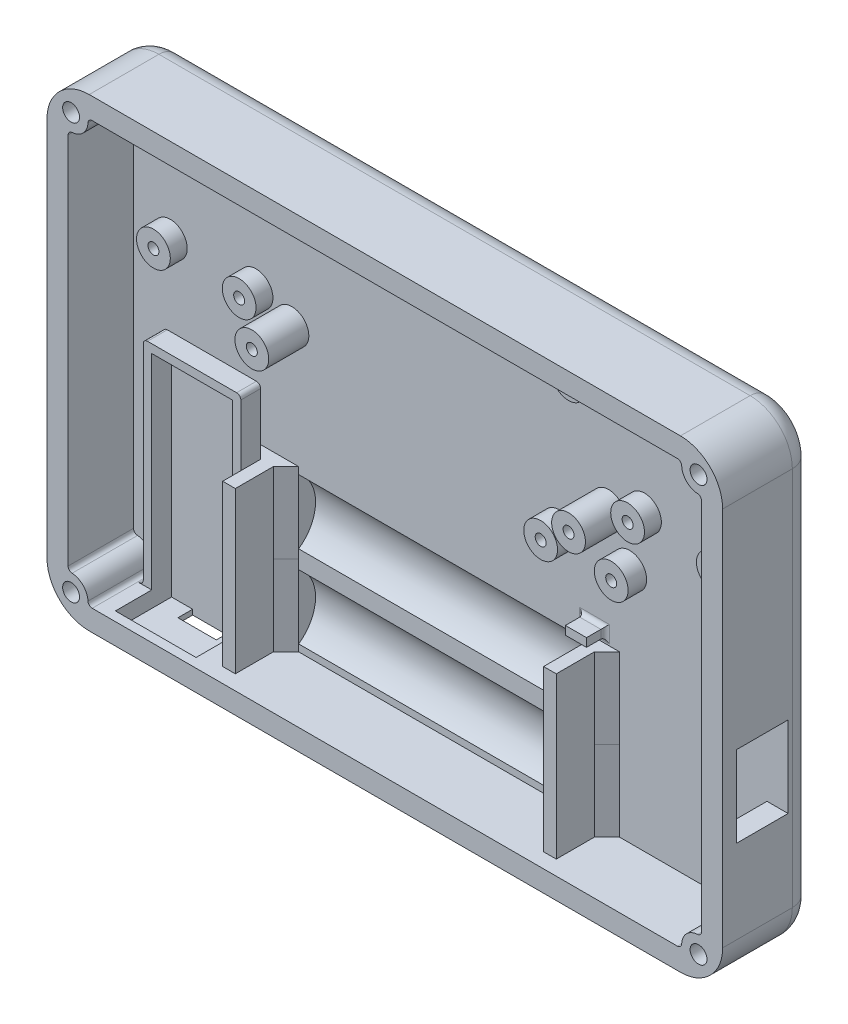
SolidWorks part; units mm, degrees
ref_plane "Ön Düzlem" through (0, 0, 0) normal (0, 0, 1) x (1, 0, 0)
ref_plane "Üst Düzlem" through (0, 0, 0) normal (0, 1, 0) x (1, 0, 0)
ref_plane "Sağ Düzlem" through (0, 0, 0) normal (1, 0, 0) x (0, 0, -1)
sketch "Çizim1" plane through (0, 0, 0) normal (0, 0, 1) x (1, 0, 0)
  line L1 (-75, -50) -> (75, -50)
  line L2 (-75, -50) -> (-75, 50)
  line L3 (-75, 50) -> (75, 50)
  line L4 (75, -50) -> (75, 50)
  line L5 (-75, -50) -> (75, 50) construction
  line L6 (-75, 50) -> (75, -50) construction
  line L7 (-80, -55) -> (80, -55)
  line L8 (-80, -55) -> (-80, 55)
  line L9 (-80, 55) -> (80, 55)
  line L10 (80, -55) -> (80, 55)
  line L11 (-80, -55) -> (80, 55) construction
  line L12 (-80, 55) -> (80, -55) construction
  point P0 (0, 0)
  point P6 (0, 0)
  dimension "D1" = 150
  dimension "D2" = 100
  dimension "D3" = 5
  dimension "D4" = 5
extrude "Yükseklik-Ekstrüzyon1" add sketch "Çizim1" along normal blind 15.5
sketch "Çizim2" plane through (0, 0, 0) normal (0, 0, -1) x (-1, 0, 0)
  line L0 (80, -55) -> (-80, -55) construction
  line L1 (80, 55) -> (80, -55) construction
  line L2 (-80, 55) -> (80, 55) construction
  line L3 (-80, -55) -> (-80, 55) construction
  line L4 (80, -55) -> (-80, -55)
  line L5 (80, 55) -> (80, -55)
  line L6 (-80, 55) -> (80, 55)
  line L7 (-80, -55) -> (-80, 55)
extrude "Yükseklik-Ekstrüzyon2" add sketch "Çizim2" along normal blind 6
fillet "Radyus1" radius 10 4 edges at (-80, -55, 4.75) (80, -55, 4.75) (80, 55, 4.75) (-80, 55, 4.75)
fillet "Radyus2" radius 5 8 edges at (77.0711, -52.0711, -6) (80, 0, -6) (77.0711, 52.0711, -6) (0, 55, -6) (-77.0711, 52.0711, -6) (-80, 0, -6) (-77.0711, -52.0711, -6) (0, -55, -6)
sketch "Çizim3" plane through (0, -55, 0) normal (0, -1, 0) x (1, 0, 0)
  line L0 (-80, -1) -> (-80, 15.5) construction
  line L1 (-61, 0) -> (-51.9, 0)
  line L2 (-61, 0) -> (-61, 3.5)
  line L3 (-61, 3.5) -> (-51.9, 3.5)
  line L4 (-51.9, 0) -> (-51.9, 3.5)
  point P4 (-56.45, 0)
  dimension "D1" = 3.5
  dimension "D2" = 9.1
  dimension "D3" = 23.55
extrude "Kes-Ekstrüzyon1" cut sketch "Çizim3" against normal up to next
sketch "Çizim4" plane through (0, 0, 0) normal (0, 0, 1) x (1, 0, 0)
  line L0 (-66, -50) -> (-66, -1.5)
  line L2 (-66, -1.5) -> (-46.9, -1.5)
  line L3 (-46.9, -1.5) -> (-46.9, -50)
  line L6 (-75, -50) -> (75, -50) construction
  line L7 (-68, -50) -> (-66, -50)
  line L8 (-68, -50) -> (-68, 0.5)
  line L9 (-68, 0.5) -> (-44.9, 0.5)
  line L10 (-44.9, -50) -> (-44.9, 0.5)
  line L11 (-46.9, -50) -> (-44.9, -50)
  line L12 (-75, -50) -> (-61, -50) construction
  line L13 (-80, 45) -> (-80, -45) construction
  point P8 (0, 0)
  point P11 (0, 0)
  point P14 (-56.55, -50)
  point P15 (-56.55, -50)
  point P18 (-66.9857, -50)
  point P19 (0, 0)
  dimension "D1" = 19.1
  dimension "D2" = 48.5
  dimension "D3" = 2
  dimension "D4" = 2
  dimension "D5" = 2
  dimension "D6" = 12
extrude "Yükseklik-Ekstrüzyon3" add sketch "Çizim4" along normal blind 4.7
sketch "Çizim6" plane through (0, -50, 0) normal (0, 1, 0) x (1, 0, 0)
  line L0 (-46.9, -4.7) -> (-46.9, 0) construction
  line L1 (-66, 0) -> (-46.9, 0)
  line L2 (-66, 0) -> (-66, -9.5)
  line L3 (-66, -9.5) -> (-46.9, -9.5)
  line L4 (-46.9, 0) -> (-46.9, -9.5)
  line L5 (-51.9, 0) -> (-46.9, 0) construction
  line L6 (-75, -15.5) -> (75, -15.5) construction
  point P4 (-45.966, 0)
  point P5 (-47.0955, 0)
  point P9 (-46.8488, -9.5)
  point P12 (-46.9, 0)
  dimension "D1" = 6
extrude "Kes-Ekstrüzyon2" cut sketch "Çizim6" against normal blind 3.8
chamfer "Pah1" distance 3.8 angle 45 1 edges at (-56.45, -50, 9.5)
ref_plane "Düzlem1" through (-35.9, 0, 0) normal (1, 0, 0) x (0, 0, -1)
sketch "Çizim7" plane through (-35.9, 0, 0) normal (1, 0, 0) x (0, 0, -1)
  line L0 (6, 45) -> (6, -45) construction
  line L1 (-13.3, -50) -> (-4.7, -50) construction
  circle A0 centre (-5.25, -40.75) radius 9.25
  point P2 (-5.25, -39.2135)
  dimension "D1" = 18.5
  dimension "D2" = 2
extrude "Kes-Ekstrüzyon3" cut sketch "Çizim7" along normal blind 67
sketch "Çizim10" plane through (0, 0, 0) normal (0, 0, 1) x (1, 0, 0)
  line L0 (-70.2916, 50) -> (-70.2916, 49.1931)
  line L1 (75, 50) -> (-75, 50) construction
  line L2 (-74.2916, 45.1931) -> (-75, 45.1931)
  line L3 (-75, 50) -> (-75, -50) construction
  line L4 (0, 0) -> (0, 50) construction
  line L5 (0, 0) -> (-75, 0) construction
  line L6 (-74.2916, -45.1931) -> (-75, -45.1931)
  line L7 (-70.2916, -50) -> (-70.2916, -49.1931)
  line L8 (70.2916, -50) -> (70.2916, -49.1931)
  line L9 (74.2916, -45.1931) -> (75, -45.1931)
  line L10 (74.2916, 45.1931) -> (75, 45.1931)
  line L11 (70.2916, 50) -> (70.2916, 49.1931)
  arc A4 (-70.2916, 49.1931) -> (-74.2916, 45.1931) centre (-74.2916, 49.1931) cw
  arc A8 (-70.2916, -49.1931) -> (-74.2916, -45.1931) centre (-74.2916, -49.1931) ccw
  arc A9 (70.2916, -49.1931) -> (74.2916, -45.1931) centre (74.2916, -49.1931) cw
  arc A10 (70.2916, 49.1931) -> (74.2916, 45.1931) centre (74.2916, 49.1931) ccw
  line M10 (-44.9, -50) -> (75, -50)
  line M11 (75, -50) -> (75, 50)
  line M12 (75, 50) -> (-75, 50)
  line M13 (-75, 50) -> (-75, -50)
  line M14 (-75, -50) -> (-68, -50)
extrude "Yükseklik-Ekstrüzyon7" add sketch "Çizim10" along normal through all contours A4 L0 L2 M12 M13 | L7 A8 L6 M13 M14 | A9 L8 L9 M10 M11 | L11 A10 L10 M11 M12 region at (-72.907, -47.8666, 0) region at (72.907, -47.8666, 0) region at (72.907, 47.8666, 0) region at (-72.907, 47.8666, 0)
sketch "Çizim11" plane through (0, 0, 15.5) normal (0, 0, 1) x (1, 0, 0)
  line L0 (0, 0) -> (0, 50) construction
  line L1 (70.2916, 50) -> (-70.2916, 50) construction
  line L2 (-74.2916, 45.1931) -> (-75, 45.1931) construction
  line L3 (0, 0) -> (-75, 0) construction
  line L4 (-75, 45.1931) -> (-75, -45.1931) construction
  circle A0 centre (-74.292, 49.1927) radius 2
  circle A1 centre (74.292, 49.1927) radius 2
  circle A2 centre (74.292, -49.1927) radius 2
  arc A3 (-70, 55) -> (-80, 45) centre (-70, 45) ccw construction
  circle A4 centre (-74.292, -49.1927) radius 2
  dimension "D1" = 4
  dimension "D2" = 2
  dimension "D3" = 3.9996
extrude "Kes-Ekstrüzyon4" cut sketch "Çizim11" against normal blind 10
sketch "Çizim8" plane through (0, 0, 0) normal (0, 0, 1) x (1, 0, 0)
  line L4 (70.2916, 50) -> (-70.2916, 50) construction
  line L6 (-70.2916, 44.3552) -> (-70.2916, 42.757) construction
  line L7 (-70.2916, 50) -> (-70.2916, 49.1931) construction
  line L8 (0, 0) -> (0, 50) construction
  line L9 (70.2916, 50) -> (-70.2916, 50) construction
  line L10 (70.2916, 44.3552) -> (70.2916, 42.757) construction
  circle A0 centre (-66.2916, 46.312) radius 4
  circle A1 centre (-45.9916, 46.312) radius 4
  circle A2 centre (-66.2916, 19.512) radius 4
  circle A3 centre (-45.9916, 19.512) radius 4
  circle A4 centre (-66.2916, 46.312) radius 1.3
  circle A5 centre (-45.9916, 46.312) radius 1.3
  circle A6 centre (-45.9916, 19.512) radius 1.3
  circle A7 centre (-66.2916, 19.512) radius 1.3
  circle A8 centre (66.2916, 19.512) radius 1.3
  circle A9 centre (45.9916, 19.512) radius 1.3
  circle A10 centre (45.9916, 46.312) radius 1.3
  circle A11 centre (66.2916, 46.312) radius 1.3
  circle A12 centre (45.9916, 19.512) radius 4
  circle A13 centre (66.2916, 19.512) radius 4
  circle A14 centre (45.9916, 46.312) radius 4
  circle A15 centre (66.2916, 46.312) radius 4
  dimension "D1" = 8
  dimension "D2" = 18.8
  dimension "D4" = 2.6
  dimension "D6" = 34.488
  dimension "D3" = 20.3
extrude "Yükseklik-Ekstrüzyon8" add sketch "Çizim8" along normal blind 4
sketch "Çizim12" plane through (0, 0, 0) normal (0, 0, 1) x (1, 0, 0)
  line L6 (44.4429, 50) -> (-44.4429, 50) construction
  circle A0 centre (-37.4916, 47) radius 4
  circle A1 centre (-37.4916, 16) radius 4
  circle A2 centre (37.5084, 16) radius 4
  circle A3 centre (37.5084, 47) radius 4
  arc A4 (-47.5404, 50) -> (-44.4429, 50) centre (-45.9916, 46.312) ccw construction
  circle A5 centre (-37.4916, 47) radius 2.8
  circle A9 centre (-37.4916, 47) radius 1.3
  circle A10 centre (-37.4916, 16) radius 1.3
  circle A11 centre (37.5084, 47) radius 1.3
  circle A12 centre (37.5084, 16) radius 1.3
  line M15 (44.4429, 50) -> (-44.4429, 50)
  dimension "D1" = 83
  dimension "D2" = 0.5
  dimension "D3" = 2.6
  dimension "D4" = 33.6
  dimension "D5" = 8
  dimension "D6" = 35.3
  dimension "D7" = 1.5
extrude "Yükseklik-Ekstrüzyon9" add sketch "Çizim12" along normal blind 9.5 contours A1 A10 | A2 A12 | A3 A11 M15 | A5 A9 region at (37.5084, 49.8937, 0) region at (-41.3785, 16, 0) region at (33.6215, 16, 0) region at (-40.2124, 47, 0)
sketch "Çizim13" plane through (75, 0, 0) normal (-1, 0, 0) x (0, 0, 1)
  line L0 (-1, 45) -> (-1, -45) construction
  line L1 (0, -5.9931) -> (12.2, -5.9931)
  line L2 (0, -5.9931) -> (0, -25.1931)
  line L3 (0, -25.1931) -> (12.2, -25.1931)
  line L4 (12.2, -5.9931) -> (12.2, -25.1931)
  line L5 (15.5, -45.1931) -> (0, -45.1931) construction
  dimension "D1" = 12.2
  dimension "D2" = 19.2
  dimension "D3" = 20
  dimension "D4" = 1
extrude "Kes-Ekstrüzyon6" cut sketch "Çizim13" against normal blind 9.5
sketch "Çizim14" plane through (0, 0, 0) normal (0, 0, 1) x (1, 0, 0)
  line L0 (-35.9, -48.3658) -> (-35.9, -33.1342) construction
  line L1 (-41.9, -31) -> (-38.9, -31)
  line L2 (-41.9, -31) -> (-41.9, -50)
  line L3 (-41.9, -50) -> (-38.9, -50)
  line L4 (-38.9, -31) -> (-38.9, -50)
  line L5 (-2.4, -48.3658) -> (-2.4, -33.1342) construction
  line L6 (31.1, -48.3658) -> (-35.9, -48.3658) construction
  line L7 (-35.9, -33.1342) -> (31.1, -33.1342) construction
  line L13 (34.1, -31) -> (34.1, -50)
  line L14 (37.1, -50) -> (34.1, -50)
  line L15 (37.1, -31) -> (37.1, -50)
  line L16 (37.1, -31) -> (34.1, -31)
  line L17 (-44.9, -50) -> (70.2916, -50) construction
  point P20 (0, 0)
  dimension "D1" = 19
  dimension "D2" = 3
  dimension "D3" = 3
extrude "Yükseklik-Ekstrüzyon10" add sketch "Çizim14" along normal blind 12
chamfer "Pah2" distance 3 angle 45 4 edges at (-41.9, -40.5, 0) (-38.9, -40.5, 0) (37.1, -40.5, 0) (34.1, -40.5, 0)
sketch "Çizim15" plane through (0, 0, 0) normal (0, 0, 1) x (1, 0, 0)
  line L5 (36.6584, -8.6) -> (31.6584, -8.6)
  line L6 (36.6584, -8.6) -> (36.6584, -10.6)
  line L7 (36.6584, -10.6) -> (31.6584, -10.6)
  line L8 (31.6584, -8.6) -> (31.6584, -10.6)
  circle A0 centre (25.8084, 6) radius 4
  circle A1 centre (42.5084, 6) radius 4
  circle A2 centre (25.8084, 6) radius 1.3
  circle A3 centre (42.5084, 6) radius 1.3
  circle A6 centre (37.5084, 16) radius 4 construction
  point P6 (34.1584, -8.6)
  dimension "D1" = 8
  dimension "D2" = 8
  dimension "D4" = 2.6
  dimension "D5" = 2.6
  dimension "D7" = 5
  dimension "D6" = 2
  dimension "D3" = 16.7
  dimension "D8" = 16.6
  dimension "D9" = 8.35
  dimension "D10" = 5
  dimension "D11" = 2
extrude "Yükseklik-Ekstrüzyon11" add sketch "Çizim15" along normal blind 4.4
fillet "Radyus4" radius 1 21 edges at (-70.2916, 50, 7.75) (-75, 45.1931, 7.75) (-70.2916, -50, 7.75) (-75, -45.1931, 7.75) (70.2916, -50, 7.75) (75, -45.1931, 7.75) (75, 45.1931, 7.75) (64.7429, 50, 2) (34.8626, 50, 4.75) (40.1541, 50, 4.75) (47.5404, 50, 2) (-64.7429, 50, 2) (-68, -50, 2.35) (-44.9, -50, 2.35) (-68, 0.5, 2.35) (-44.9, 0.5, 2.35) (70.2916, 50, 7.75) (34.1584, -10.6, 0) (36.6584, -9.6, 0) (34.1584, -8.6, 0) (31.6584, -9.6, 0)
ref_plane "Düzlem2" through (0, -31, 0) normal (0, 1, 0) x (1, 0, 0)
mirror "Aynalama1" about plane through (0, -31, 0) normal (0, 1, 0) of "Pah2", "Kes-Ekstrüzyon3", "Yükseklik-Ekstrüzyon10"
